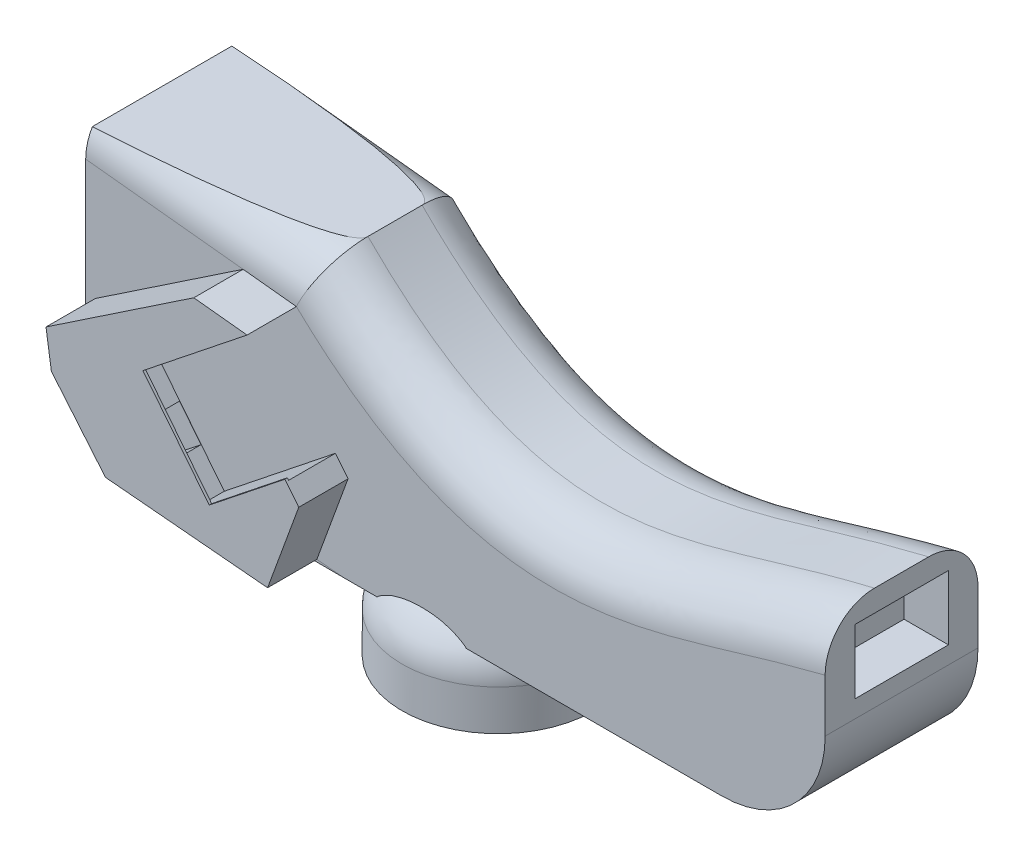
SolidWorks part; units mm, degrees
ref_plane "前基準面" through (0, 0, 0) normal (0, 0, 1) x (1, 0, 0)
ref_plane "上基準面" through (0, 0, 0) normal (0, 1, 0) x (1, 0, 0)
ref_plane "右基準面" through (0, 0, 0) normal (1, 0, 0) x (0, 0, -1)
sketch "草圖1" plane through (0, 0, 0) normal (0, 0, 1) x (1, 0, 0)
  line L0 (0, 0) -> (0, 60)
  line L1 (0, 60) -> (30.6281, 60)
  line L2 (30.6281, 60) -> (78.9616, 54.8725)
  line L3 (280.2175, 30) -> (280.2175, 0)
  line L4 (280.2175, 0) -> (227.8434, 0)
  line L5 (153.3118, -9.6901) -> (107.7898, -9.6901)
  spline S0 degree 3 poles (78.9616, 54.8725) (112.2329, 21.4354) (171.3693, 45.9237) (246.5881, 58.3745) (280.2175, 30) knots 0 0 0 0 0.429026 1 1 1 1
  spline S1 degree 1 poles (227.8434, 0) (153.3118, -9.6901) knots 0 0 1 1
  spline S2 degree 1 poles (107.7898, -9.6901) (0, 0) knots 0 0 1 1
  dimension "D1" = 30
  dimension "D2" = 60
extrude "填料-伸長1" add sketch "草圖1" along normal blind 31
fillet "圓角3" radius 10 9 edges at (0, 30, 31) (15.3141, 60, 31) (54.7949, 57.4363, 31) (280.2175, 15, 31) (254.0304, 0, 31) (130.5508, -9.6901, 31)
fillet "圓角4" radius 10 9 edges at (130.5508, -9.6901, 0) (254.0304, 0, 0) (280.2175, 15, 0) (54.7949, 57.4363, 0) (15.3141, 60, 0) (0, 30, 0)
ref_plane "平面1" through (0, -11, 0) normal (0, 1, 0) x (1, 0, 0)
ref_plane "平面2" through (0, 0, 0) normal (1, 0, 0) x (0, 0, -1)
sketch "草圖9" plane through (0, 0, 0) normal (1, 0, 0) x (0, 0, -1)
  line L0 (-15.5, -940) -> (-15.5, 49060) construction
  line L1 (-21, 60) -> (-10, 60) construction
  line L2 (-1000, 29.5707) -> (49000, 29.5707) construction
  line L3 (0, 9.1413) -> (0, 50) construction
  line L5 (-2.5, 39.1457) -> (-28.5, 39.1457)
  line L6 (-2.5, 39.1457) -> (-2.5, 19.9957)
  line L7 (-2.5, 19.9957) -> (-28.5, 19.9957)
  line L8 (-28.5, 39.1457) -> (-28.5, 19.9957)
  line L9 (-2.5, 39.1457) -> (-28.5, 19.9957) construction
  line L10 (-2.5, 19.9957) -> (-28.5, 39.1457) construction
  point P5 (-15.5, 60)
  point P6 (-15.5, 29.5707)
  point P10 (0, 29.5707)
  dimension "D1" = 26
  dimension "D2" = 19.15
extrude "除料-伸長1" cut sketch "草圖9" along normal blind 70
sketch "草圖11" plane through (70, 0, 0) normal (-1, 0, 0) x (0, 0, 1)
  line L0 (10, 39.1457) -> (21, 39.1457) construction
  line L1 (4.5, 37.1457) -> (26.5, 37.1457)
  line L2 (4.5, 37.1457) -> (4.5, 21.9957)
  line L3 (4.5, 21.9957) -> (26.5, 21.9957)
  line L4 (26.5, 37.1457) -> (26.5, 21.9957)
  line L5 (4.5, 37.1457) -> (26.5, 21.9957) construction
  line L6 (4.5, 21.9957) -> (26.5, 37.1457) construction
  line L7 (28.5, 19.9957) -> (2.5, 19.9957) construction
  line L8 (2.5, 19.9957) -> (2.5, 39.1457) construction
  line L9 (28.5, 39.1457) -> (28.5, 19.9957) construction
  point P0 (15.5, 29.5707)
  dimension "D1" = 2
  dimension "D2" = 2
  dimension "D3" = 2
  dimension "D4" = 2
extrude "除料-伸長4" cut sketch "草圖11" against normal blind 22
sketch "草圖12" plane through (0, 0, 31) normal (0, 0, 1) x (1, 0, 0)
  line L1 (280.2175, 0) -> (250.2175, 0)
  line L2 (280.2175, 0) -> (280.2175, 58.699)
  line L3 (280.2175, 58.699) -> (250.2175, 58.699)
  line L4 (250.2175, 0) -> (250.2175, 58.699)
  dimension "D1" = 30
extrude "除料-伸長5" cut sketch "草圖12" against normal blind 54
sketch "草圖15" plane through (0, 0, 31) normal (0, 0, 1) x (1, 0, 0)
  line L0 (30.0992, 50) -> (74.4514, 45.2949)
  line L1 (74.4514, 45.2949) -> (87.8973, 28.3987)
  line L2 (87.8973, 28.3987) -> (78.608, 2.9736)
  line L3 (10, 9.1413) -> (108.2383, 0.3099) construction
  line L4 (78.608, 2.9736) -> (36.6069, 6.7494)
  line L5 (36.6069, 6.7494) -> (30.0992, 50)
extrude "填料-伸長2" add sketch "草圖15" along normal blind 10
sketch "草圖20" plane through (0, 0, 41) normal (0, 0, 1) x (1, 0, 0)
  line L0 (63.6448, 46.4413) -> (33.6621, 26.3206)
  line L1 (74.4514, 45.2949) -> (30.0992, 50) construction
  line L2 (30.0992, 50) -> (36.6069, 6.7494) construction
  line L3 (33.6621, 26.3206) -> (30.0992, 50)
  line L4 (30.0992, 50) -> (63.6448, 46.4413)
extrude "除料-伸長9" cut sketch "草圖20" against normal blind 10
sketch "草圖23" plane through (0, 0, 41) normal (0, 0, 1) x (1, 0, 0)
  line L0 (36.6069, 6.7494) -> (45.7263, 5.9296)
  line L1 (36.6069, 6.7494) -> (78.608, 2.9736) construction
  line L2 (45.7263, 5.9296) -> (34.753, 19.0707)
  line L3 (33.6621, 26.3206) -> (36.6069, 6.7494) construction
  line L4 (34.753, 19.0707) -> (36.6069, 6.7494)
extrude "除料-伸長16" cut sketch "草圖23" against normal blind 10 contours L2 L4 L0
sketch "草圖26" plane through (67.6528, 53.838, 0) normal (0.7825, 0.6227, 0) x (0, 0, -1)
  line L0 (-41, -32.5115) -> (-41, -10.9181) construction
  line L1 (-31, -10.9181) -> (-40.5, -10.9181)
  line L2 (-31, -10.9181) -> (-31, -32.9181)
  line L3 (-31, -32.9181) -> (-40.5, -32.9181)
  line L4 (-40.5, -10.9181) -> (-40.5, -32.9181)
  dimension "D1" = 22
  dimension "D2" = 0.5
extrude "除料-伸長17" cut sketch "草圖26" against normal blind 36.2
sketch "草圖27" plane through (39.3274, 31.2966, 0) normal (0.7825, 0.6227, 0) x (0, 0, -1)
  line L0 (-35.75, -1011.4065) -> (-35.75, 48988.5935) construction
  line L1 (-31, -10.9181) -> (-40.5, -10.9181) construction
  line L2 (-1040.5, -21.9181) -> (48959.5, -21.9181) construction
  line L3 (-40.5, -10.9181) -> (-40.5, -32.9181) construction
  line L5 (-38.26, -18.4181) -> (-33.24, -18.4181)
  line L6 (-38.26, -18.4181) -> (-38.26, -25.4181)
  line L7 (-38.26, -25.4181) -> (-33.24, -25.4181)
  line L8 (-33.24, -18.4181) -> (-33.24, -25.4181)
  line L9 (-38.26, -18.4181) -> (-33.24, -25.4181) construction
  line L10 (-38.26, -25.4181) -> (-33.24, -18.4181) construction
  point P5 (-35.75, -10.9181)
  point P6 (-35.75, -21.9181)
  point P10 (-40.5, -21.9181)
  dimension "D1" = 7
  dimension "D2" = 5.02
extrude "除料-伸長18" cut sketch "草圖27" against normal blind 36.2
sketch "草圖28" plane through (0, 0, 40.5) normal (0, 0, -1) x (-1, 0, 0)
  line L0 (-77.1009, 41.9655) -> (-49.032, 19.1055) construction
  line L1 (-87.8973, 28.3987) -> (-74.4514, 45.2949) construction
  dimension "D1" = 36.2
sketch "草圖29" plane through (67.6528, 53.838, 0) normal (0.7825, 0.6227, 0) x (0, 0, -1)
  line L0 (-41, -10.9181) -> (-40.5, -10.9181)
  line L1 (-40.5, -10.9181) -> (-40.5, -32.5115)
  line L2 (-40.5, -32.5115) -> (-41, -32.5115)
  line L3 (-41, -32.5115) -> (-41, -10.9181)
extrude "除料-伸長19" cut sketch "草圖29" against normal blind 30
sketch "草圖31" plane through (0, 0, 0) normal (0, 0, -1) x (-1, 0, 0)
  line L0 (75.0986, -11) -> (-75.0986, -11) construction
  line L1 (0, -11) -> (-31.7159, -11)
  line L2 (0, -11) -> (0, 70.0151)
  line L3 (0, 70.0151) -> (-31.7159, 70.0151)
  line L4 (-31.7159, -11) -> (-31.7159, 70.0151)
  line L5 (0, 17.3572) -> (0, -17.3572) construction
extrude "除料-伸長20" cut sketch "草圖31" against normal blind 97
sketch "草圖34" plane through (0, 0, 0) normal (0, 0, -1) x (-1, 0, 0)
  line L0 (75.0986, -11) -> (-75.0986, -11) construction
  line L1 (-255.1694, 57.7573) -> (-219.2353, 57.7573)
  line L2 (-255.1694, 57.7573) -> (-255.1694, -11)
  line L3 (-255.1694, -11) -> (-219.2353, -11)
  line L4 (-219.2353, 57.7573) -> (-219.2353, -11)
extrude "除料-伸長21" cut sketch "草圖34" against normal blind 97
sketch "草圖38" plane through (0, -11, 0) normal (0, 1, 0) x (1, 0, 0)
  line L0 (69.7528, -1010) -> (69.7528, 48990) construction
  line L1 (31.7159, -10) -> (107.7898, -10) construction
  line L2 (-968.2841, -15.5) -> (49031.7159, -15.5) construction
  line L3 (31.7159, -21) -> (31.7159, -10) construction
  line L5 (52.2528, -8) -> (87.2528, -8)
  line L6 (52.2528, -8) -> (52.2528, -23)
  line L7 (52.2528, -23) -> (87.2528, -23)
  line L8 (87.2528, -8) -> (87.2528, -23)
  line L9 (52.2528, -8) -> (87.2528, -23) construction
  line L10 (52.2528, -23) -> (87.2528, -8) construction
  point P5 (69.7528, -10)
  point P6 (69.7528, -15.5)
  point P10 (31.7159, -15.5)
  dimension "D1" = 15
  dimension "D2" = 35
extrude "除料-伸長23" cut sketch "草圖38" along normal blind 37
sketch "草圖39" plane through (0, 0, 0) normal (0, 0, -1) x (-1, 0, 0)
  line L0 (75.0986, -11) -> (-75.0986, -11) construction
  line L1 (-219.2353, 49.8813) -> (-204.2353, 49.8813)
  line L2 (-219.2353, 49.8813) -> (-219.2353, -11)
  line L3 (-219.2353, -11) -> (-204.2353, -11)
  line L4 (-204.2353, 49.8813) -> (-204.2353, -11)
  dimension "D1" = 15
extrude "除料-伸長24" cut sketch "草圖39" against normal blind 37
sketch "草圖40" plane through (70, 0, 0) normal (-1, 0, 0) x (0, 0, 1)
  line L0 (4.5, 21.9957) -> (4.5, 19.9957)
  line L1 (28.5, 19.9957) -> (2.5, 19.9957) construction
  line L2 (4.5, 21.9957) -> (26.5, 21.9957)
  line L3 (26.5, 21.9957) -> (26.5, 19.9957)
  line L4 (26.5, 19.9957) -> (4.5, 19.9957)
extrude "除料-伸長26" cut sketch "草圖40" against normal blind 23
sketch "草圖46" plane through (0, 0, 0) normal (0, 0, -1) x (-1, 0, 0)
  line L0 (75.0986, -11) -> (-75.0986, -11) construction
  line L1 (-204.2353, 48.7112) -> (-181.7153, 48.7112)
  line L2 (-204.2353, 48.7112) -> (-204.2353, -11)
  line L3 (-204.2353, -11) -> (-181.7153, -11)
  line L4 (-181.7153, 48.7112) -> (-181.7153, -11)
  dimension "D1" = 22.52
extrude "除料-伸長27" cut sketch "草圖46" against normal blind 59
sketch "草圖50" plane through (0, 0, 41) normal (0, 0, 1) x (1, 0, 0)
  line L0 (82.1256, 23.8056) -> (84.9311, 20.2802)
  line L1 (64.4232, 9.7181) -> (87.8973, 28.3987) construction
  line L2 (78.608, 2.9736) -> (87.6296, 27.666) construction
  line L3 (84.9311, 20.2802) -> (87.8973, 28.3987)
  line L4 (78.608, 2.9736) -> (87.8973, 28.3987) construction
  line L5 (87.8973, 28.3987) -> (82.1256, 23.8056)
extrude "除料-伸長30" cut sketch "草圖50" against normal blind 10
sketch "草圖57" plane through (44.1787, 35.1573, 0) normal (0.7825, 0.6227, 0) x (0, 0, -1)
  line L0 (-40.5, -32.5115) -> (-40.5, -10.9181) construction
  line L1 (-41, -10.9181) -> (-40.5, -10.9181)
  line L2 (-41, -10.9181) -> (-41, -32.5115)
  line L3 (-41, -32.5115) -> (-40.5, -32.5115)
  line L4 (-40.5, -10.9181) -> (-40.5, -32.5115)
extrude "填料-伸長3" add sketch "草圖57" along normal blind 3
sketch "草圖63" plane through (0, 0, 31) normal (0, 0, 1) x (1, 0, 0)
  line L0 (75.0986, -11) -> (-75.0986, -11) construction
  line L1 (192.2521, -11) -> (27.8442, -11)
  line L2 (192.2521, -11) -> (192.2521, 0)
  line L3 (192.2521, 0) -> (27.8442, 0)
  line L4 (27.8442, -11) -> (27.8442, 0)
extrude "除料-伸長34" cut sketch "草圖63" against normal blind 76
sketch "草圖65" plane through (0, 0, 31) normal (0, 0, 1) x (1, 0, 0)
  line L0 (31.7159, 7.1891) -> (31.7159, 0) construction
  line L1 (186.8562, -3.523) -> (31.7159, -3.523)
  line L2 (186.8562, -3.523) -> (186.8562, 2.472)
  line L3 (186.8562, 2.472) -> (31.7159, 2.472)
  line L4 (31.7159, -3.523) -> (31.7159, 2.472)
extrude "除料-伸長35" cut sketch "草圖65" against normal blind 76
sketch "草圖67" plane through (0, 0, 31) normal (0, 0, 1) x (1, 0, 0)
  line L0 (31.7159, 13.6752) -> (31.7159, 2.472)
  line L1 (31.7159, 49.8285) -> (31.7159, 7.1891) construction
  line L2 (31.7159, 2.472) -> (43.0787, 2.472)
  line L3 (31.7159, 2.472) -> (84.1879, 2.472) construction
  line L4 (43.0787, 2.472) -> (31.7159, 13.6752)
extrude "除料-伸長36" cut sketch "草圖67" against normal blind 76
fillet "圓角10" radius 21 1 edges at (43.0787, 2.472, 15.5)
fillet "圓角11" radius 21 1 edges at (31.7159, 13.6752, 15.5)
fillet "圓角12" radius 21 1 edges at (181.7153, 2.472, 15.5)
sketch "草圖69" plane through (0, -11, 0) normal (0, 1, 0) x (1, 0, 0)
  line L1 (52.2528, -8) -> (42.2528, -8)
  line L2 (52.2528, -8) -> (52.2528, -23)
  line L3 (52.2528, -23) -> (42.2528, -23)
  line L4 (42.2528, -8) -> (42.2528, -23)
  dimension "D1" = 10
extrude "除料-伸長37" cut sketch "草圖69" along normal blind 42
sketch "草圖71" plane through (39.3274, 31.2966, 0) normal (0.7825, 0.6227, 0) x (0, 0, -1)
  line L1 (-33.24, -18.4181) -> (-31.04, -18.4181)
  line L2 (-33.24, -18.4181) -> (-33.24, -25.4181)
  line L3 (-33.24, -25.4181) -> (-31.04, -25.4181)
  line L4 (-31.04, -18.4181) -> (-31.04, -25.4181)
  dimension "D1" = 2.2
extrude "除料-伸長38" cut sketch "草圖71" against normal blind 42
sketch "草圖72" plane through (0, 0, 31) normal (0, 0, 1) x (1, 0, 0)
  line L1 (31.7159, 59.8846) -> (78.9616, 59.8846)
  line L2 (31.7159, 59.8846) -> (31.7159, 54.8725)
  line L3 (31.7159, 54.8725) -> (78.9616, 54.8725)
  line L4 (78.9616, 59.8846) -> (78.9616, 54.8725)
extrude "除料-伸長39" cut sketch "草圖72" against normal blind 42
sketch "草圖74" plane through (181.7153, 0, 0) normal (1, 0, 0) x (0, 0, -1)
  line L0 (-31, 23.472) -> (-31, 34.1737) construction
  line L1 (-25, 40.0627) -> (-6, 40.0627)
  line L2 (-25, 40.0627) -> (-25, 27.004)
  line L3 (-25, 27.004) -> (-6, 27.004)
  line L4 (-6, 40.0627) -> (-6, 27.004)
  line L5 (-25, 40.0627) -> (-6, 27.004) construction
  line L6 (-25, 27.004) -> (-6, 40.0627) construction
  line L7 (0, 23.472) -> (0, 34.1737) construction
  point P0 (-15.5, 33.5333)
  point P9 (0, 28.8228)
  dimension "D1" = 6
  dimension "D2" = 6
extrude "除料-伸長40" cut sketch "草圖74" against normal blind 9
sketch "草圖75" plane through (0, -11, 0) normal (0, 1, 0) x (1, 0, 0)
  line L0 (-957.7472, -15.5) -> (49042.2528, -15.5) construction
  line L1 (42.2528, -8) -> (42.2528, -23) construction
  circle A0 centre (99.8747, -15.5) radius 11.5
  point P5 (42.2528, -15.5)
  dimension "D1" = 23
extrude "伸長-薄件1" add sketch "草圖75" along normal blind 18 separate body thin thin type one direction wall 8
fillet "圓角13" radius 10 1 edges at (119.3747, 7, 15.5)
